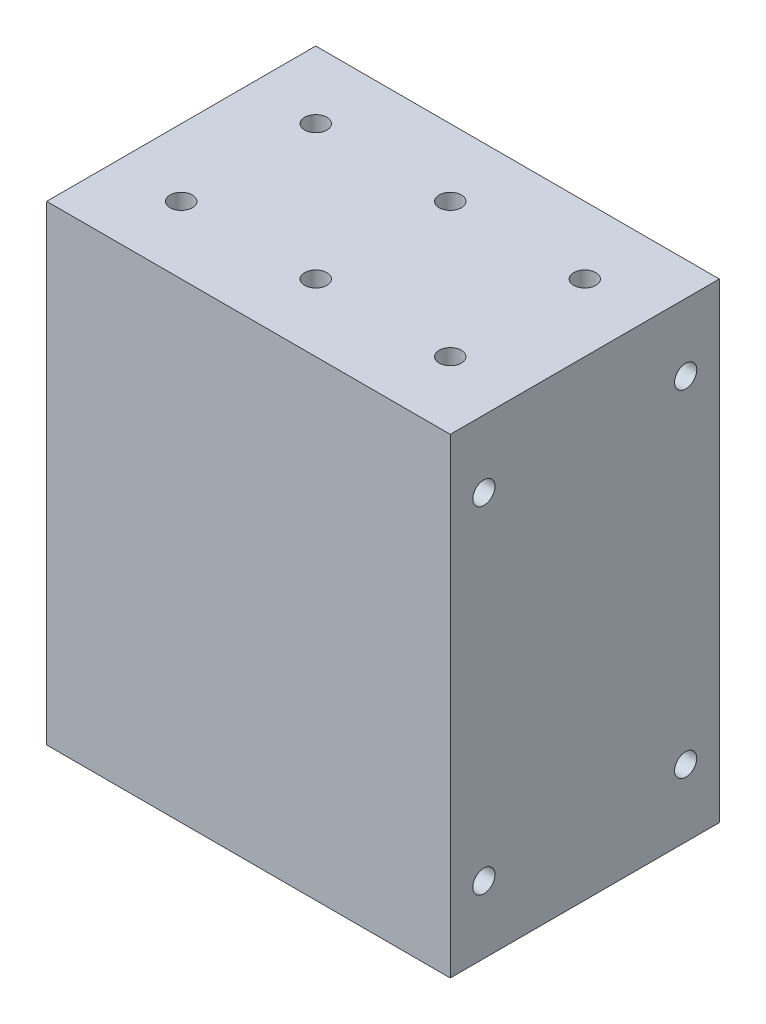
SolidWorks part; units mm, degrees
ref_plane "Front Plane" through (0, 0, 0) normal (0, 0, 1) x (1, 0, 0)
ref_plane "Top Plane" through (0, 0, 0) normal (0, 1, 0) x (1, 0, 0)
ref_plane "Right Plane" through (0, 0, 0) normal (1, 0, 0) x (0, 0, -1)
sketch "Sketch1" plane through (0, 0, 0) normal (0, 1, 0) x (1, 0, 0)
  line L1 (-30, -20) -> (30, -20)
  line L2 (-30, -20) -> (-30, 20)
  line L3 (-30, 20) -> (30, 20)
  line L4 (30, -20) -> (30, 20)
  line L5 (-30, -20) -> (30, 20) construction
  line L6 (-30, 20) -> (30, -20) construction
  point P0 (0, 0)
  dimension "D1" = 40
  dimension "D2" = 60
extrude "Boss-Extrude1" add sketch "Sketch1" along normal blind 70
hole_wizard "M4x0.7 Tapped Hole1" positions "Sketch2" profile "Sketch4" tap size "M4x0.7" standard "ANSI Metric"
sketch "Sketch2" plane through (0, 70, 0) normal (0, 1, 0) x (1, 0, 0)
  line L0 (-30, 20) -> (-30, -20) construction
  line L1 (30, 20) -> (-30, 20) construction
  point P0 (-20, 10)
  point P15 (0, 10)
  point P16 (20, 10)
  point P17 (0, -10)
  point P18 (20, -10)
  point P19 (-20, -10)
  dimension "D1" = 10
  dimension "D2" = 10
  dimension "D3" = 3
  dimension "D4" = 2
sketch "Sketch4" plane through (-20, 70, -10) normal (1, 0, 0) x (0, 0, 1)
  line L0 (0, 0) -> (0, 15.9914)
  line L1 (0, 15.9914) -> (1.65, 15)
  line L2 (1.65, 15) -> (1.65, 0)
  line L5 (1.65, 0) -> (0, 0)
  line L10 (0, 15.9914) -> (-1.65, 15) construction
  line L11 (0, -6.35) -> (0, 107.95) construction
  dimension "Tap Drill Dia." = 3.3
  dimension "Tap Drill Depth" = 15
  dimension "Drill Angle" = 118
cosmetic thread "Hole Thread1" parameters "D1"=8, "D2"=4
cosmetic thread "Hole Thread2" parameters "D1"=8, "D2"=4
cosmetic thread "Hole Thread3" parameters "D1"=8, "D2"=4
cosmetic thread "Hole Thread4" parameters "D1"=8, "D2"=4
cosmetic thread "Hole Thread5" parameters "D1"=8, "D2"=4
cosmetic thread "Hole Thread6" parameters "D1"=8, "D2"=4
hole_wizard "M4x0.7 Tapped Hole2" positions "Sketch5" profile "Sketch6" tap size "M4x0.7" standard "ANSI Metric"
sketch "Sketch5" plane through (0, 0, 0) normal (0, -1, 0) x (-1, 0, 0)
  line L0 (-30, 20) -> (30, 20) construction
  line L1 (-30, -20) -> (-30, 20) construction
  point P0 (-20, 10)
  point P12 (0, 10)
  point P13 (20, 10)
  point P14 (0, -10)
  point P15 (20, -10)
  point P16 (-20, -10)
  dimension "D1" = 10
  dimension "D2" = 10
  dimension "D3" = 3
  dimension "D4" = 2
sketch "Sketch6" plane through (20, 0, -10) normal (1, 0, 0) x (0, 0, -1)
  line L0 (0, 0) -> (0, 15.9914)
  line L1 (0, 15.9914) -> (1.65, 15)
  line L2 (1.65, 15) -> (1.65, 0)
  line L5 (1.65, 0) -> (0, 0)
  line L10 (0, 15.9914) -> (-1.65, 15) construction
  line L11 (0, -6.35) -> (0, 107.95) construction
  dimension "Tap Drill Dia." = 3.3
  dimension "Tap Drill Depth" = 15
  dimension "Drill Angle" = 118
cosmetic thread "Hole Thread7" parameters "D1"=8, "D2"=4
cosmetic thread "Hole Thread8" parameters "D1"=8, "D2"=4
cosmetic thread "Hole Thread9" parameters "D1"=8, "D2"=4
cosmetic thread "Hole Thread10" parameters "D1"=8, "D2"=4
cosmetic thread "Hole Thread11" parameters "D1"=8, "D2"=4
cosmetic thread "Hole Thread12" parameters "D1"=8, "D2"=4
hole_wizard "M4x0.7 Tapped Hole3" positions "Sketch7" profile "Sketch8" tap size "M4x0.7" standard "ANSI Metric"
sketch "Sketch7" plane through (0, 0, -20) normal (0, 0, -1) x (-1, 0, 0)
  line L1 (-30, 70) -> (30, 70) construction
  point P0 (-15, 55)
  point P14 (15, 55)
  point P15 (15, 15)
  point P16 (-15, 15)
  dimension "D1" = 15
  dimension "D2" = 15
  dimension "D3" = 2
  dimension "D4" = 2
sketch "Sketch8" plane through (15, 55, -20) normal (1, 0, 0) x (0, 1, 0)
  line L0 (0, 0) -> (0, 15.9914)
  line L1 (0, 15.9914) -> (1.65, 15)
  line L2 (1.65, 15) -> (1.65, 0)
  line L5 (1.65, 0) -> (0, 0)
  line L10 (0, 15.9914) -> (-1.65, 15) construction
  line L11 (0, -6.35) -> (0, 107.95) construction
  dimension "Tap Drill Dia." = 3.3
  dimension "Tap Drill Depth" = 15
  dimension "Drill Angle" = 118
cosmetic thread "Hole Thread13" parameters "D1"=8, "D2"=4
cosmetic thread "Hole Thread14" parameters "D1"=8, "D2"=4
cosmetic thread "Hole Thread15" parameters "D1"=8, "D2"=4
cosmetic thread "Hole Thread16" parameters "D1"=8, "D2"=4
hole_wizard "M4x0.7 Tapped Hole4" positions "Sketch9" profile "Sketch10" tap size "M4x0.7" standard "ANSI Metric"
sketch "Sketch9" plane through (30, 0, 0) normal (1, 0, 0) x (0, 0, -1)
  line L0 (-20, 70) -> (-20, 0) construction
  line L1 (-20, 70) -> (20, 70) construction
  point P0 (-15, 60)
  point P13 (15, 60)
  point P14 (15, 10)
  point P15 (-15, 10)
  dimension "D1" = 5
  dimension "D2" = 10
  dimension "D3" = 2
  dimension "D4" = 2
sketch "Sketch10" plane through (30, 60, 15) normal (0, 1, 0) x (0, 0, -1)
  line L0 (0, 0) -> (0, 15.9914)
  line L1 (0, 15.9914) -> (1.65, 15)
  line L2 (1.65, 15) -> (1.65, 0)
  line L5 (1.65, 0) -> (0, 0)
  line L10 (0, 15.9914) -> (-1.65, 15) construction
  line L11 (0, -6.35) -> (0, 107.95) construction
  dimension "Tap Drill Dia." = 3.3
  dimension "Tap Drill Depth" = 15
  dimension "Drill Angle" = 118
cosmetic thread "Hole Thread17" parameters "D1"=8, "D2"=4
cosmetic thread "Hole Thread18" parameters "D1"=8, "D2"=4
cosmetic thread "Hole Thread19" parameters "D1"=8, "D2"=4
cosmetic thread "Hole Thread20" parameters "D1"=8, "D2"=4
mirror "Mirror1" about plane through (0, 0, 0) normal (1, 0, 0) of "M4x0.7 Tapped Hole4"
cosmetic thread "Hole Thread21" parameters "D1"=8, "D2"=4
cosmetic thread "Hole Thread22" parameters "D1"=8, "D2"=4
cosmetic thread "Hole Thread23" parameters "D1"=8, "D2"=4
cosmetic thread "Hole Thread24" parameters "D1"=8, "D2"=4
chamfer "Chamfer1" [suppressed] distance 15 angle 45
